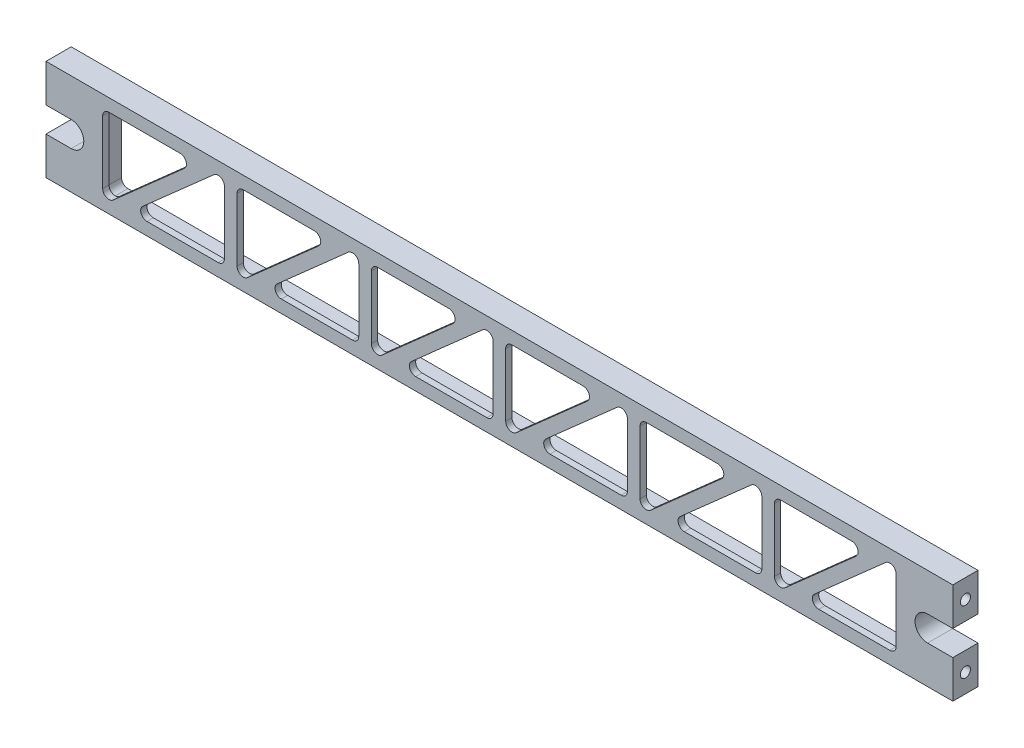
SolidWorks part; units mm, degrees
material "6061 Alloy"
ref_plane "Front Plane" through (0, 0, 0) normal (0, 0, 1) x (1, 0, 0)
ref_plane "Top Plane" through (0, 0, 0) normal (0, 1, 0) x (1, 0, 0)
ref_plane "Right Plane" through (0, 0, 0) normal (1, 0, 0) x (0, 0, -1)
sketch "Sketch1" plane through (0, 0, 0) normal (1, 0, 0) x (0, 0, -1)
  line L1 (0, 0) -> (12.7, 0)
  line L2 (0, 0) -> (0, 50.8)
  line L3 (0, 50.8) -> (12.7, 50.8)
  line L4 (12.7, 0) -> (12.7, 50.8)
  dimension "D1" = 12.7
  dimension "D2" = 50.8
extrude "Boss-Extrude1" add sketch "Sketch1" along normal mid plane 457.2
hole_wizard "1/4-20 Tapped Hole1" positions "3DSketch1" profile "Sketch2" tap size "1/4-20" standard "ANSI Inch"
sketch3d "3DSketch1"
  line L2 (228.6, 9.525, -6.35) -> (228.6, 41.275, -6.35) construction
  line L4 (228.6, 41.275, -6.35) -> (228.6, 50.8, -6.35) construction
  line L5 (228.6, 50.8, -12.7) -> (228.6, 50.8, 0) construction
  line L8 (228.6, 9.525, -6.35) -> (228.6, 0, -6.35) construction
  line L9 (228.6, 0, 0) -> (228.6, 0, -12.7) construction
  point P0 (228.6, 41.275, -6.35)
  point P2 (228.6, 9.525, -6.35)
  point P4 (-228.6, 9.525, -6.35)
  point P6 (-228.6, 41.275, -6.35)
  dimension "D1" = 31.75
sketch "Sketch2" plane through (228.6, 41.275, -6.35) normal (0, 1, 0) x (0, 0, -1)
  line L0 (0, 0) -> (0, 20.5838)
  line L1 (0, 20.5838) -> (2.5527, 19.05)
  line L2 (2.5527, 19.05) -> (2.5527, 0)
  line L5 (2.5527, 0) -> (0, 0)
  line L10 (0, 20.5838) -> (-2.5527, 19.05) construction
  line L11 (0, -6.35) -> (0, 107.95) construction
  dimension "Tap Drill Dia." = 5.1054
  dimension "Tap Drill Depth" = 19.05
  dimension "Drill Angle" = 118
sketch "Sketch4" plane through (0, 0, -12.7) normal (0, 0, -1) x (-1, 0, 0)
  line L0 (0, 0) -> (0, 3.175) construction
  line L1 (200.025, 47.625) -> (-200.025, 47.625)
  line L2 (203.2, 44.45) -> (203.2, 6.35)
  line L3 (200.025, 3.175) -> (-200.025, 3.175)
  line L4 (-203.2, 44.45) -> (-203.2, 6.35)
  line L5 (-228.6, 0) -> (228.6, 0) construction
  line L6 (0, 47.625) -> (0, 50.8) construction
  line L7 (-228.6, 50.8) -> (228.6, 50.8) construction
  line L8 (228.6, 25.4) -> (203.2, 25.4) construction
  line L9 (228.6, 0) -> (228.6, 50.8) construction
  line L10 (-228.6, 25.4) -> (-203.2, 25.4) construction
  line L11 (-228.6, 0) -> (-228.6, 50.8) construction
  arc A0 (-200.025, 3.175) -> (-203.2, 6.35) centre (-200.025, 6.35) cw
  arc A1 (-200.025, 47.625) -> (-203.2, 44.45) centre (-200.025, 44.45) ccw
  arc A2 (203.2, 6.35) -> (200.025, 3.175) centre (200.025, 6.35) cw
  arc A3 (200.025, 47.625) -> (203.2, 44.45) centre (200.025, 44.45) cw
  dimension "D1" = 3.175
  dimension "D2" = 3.175
  dimension "D3" = 25.4
extrude "Cut-Extrude1" cut sketch "Sketch4" against normal blind 9.525
sketch "Sketch5" plane through (0, 0, -3.175) normal (0, 0, -1) x (-1, 0, 0)
  line L0 (-200.025, 41.275) -> (-200.025, 9.525)
  line L1 (-196.85, 6.35) -> (-160.9784, 6.35)
  line L2 (-158.8741, 11.9025) -> (-194.7457, 43.6525)
  line L3 (-179.7926, 38.8975) -> (-143.921, 7.1475)
  line L4 (-138.6417, 9.525) -> (-138.6417, 41.275)
  line L5 (-141.8167, 44.45) -> (-177.6882, 44.45)
  line L6 (-132.2917, 41.275) -> (-132.2917, 9.525)
  line L7 (-159.7525, 44.45) -> (-159.7525, 47.625) construction
  line L8 (200.025, 47.625) -> (-200.025, 47.625) construction
  line L9 (-129.1167, 6.35) -> (-93.2451, 6.35)
  line L10 (-178.9142, 6.35) -> (-178.9142, 3.175) construction
  line L11 (-200.025, 3.175) -> (200.025, 3.175) construction
  line L12 (-91.1408, 11.9025) -> (-127.0123, 43.6525)
  line L13 (-200.025, 25.4) -> (-203.2, 25.4) construction
  line L14 (-203.2, 44.45) -> (-203.2, 6.35) construction
  line L15 (-176.8099, 27.7775) -> (-172.6013, 32.5325) construction
  line L16 (-112.0592, 38.8975) -> (-76.1877, 7.1475)
  line L17 (-70.9083, 9.525) -> (-70.9083, 41.275)
  line L18 (-74.0833, 44.45) -> (-109.9549, 44.45)
  line L19 (-109.0766, 27.7775) -> (-104.8679, 32.5325) construction
  line L20 (-64.5583, 41.275) -> (-64.5583, 9.525)
  line L21 (-61.3833, 6.35) -> (-25.5118, 6.35)
  line L22 (-23.4074, 11.9025) -> (-59.279, 43.6525)
  line L23 (-44.3259, 38.8975) -> (-8.4543, 7.1475)
  line L24 (-3.175, 9.525) -> (-3.175, 41.275)
  line L25 (-6.35, 44.45) -> (-42.2216, 44.45)
  line L26 (-41.3432, 27.7775) -> (-37.1346, 32.5325) construction
  line L27 (3.175, 41.275) -> (3.175, 9.525)
  line L28 (6.35, 6.35) -> (42.2216, 6.35)
  line L29 (44.3259, 11.9025) -> (8.4543, 43.6525)
  line L30 (23.4074, 38.8975) -> (59.279, 7.1475)
  line L31 (64.5583, 9.525) -> (64.5583, 41.275)
  line L32 (61.3833, 44.45) -> (25.5118, 44.45)
  line L33 (26.3901, 27.7775) -> (30.5987, 32.5325) construction
  line L34 (70.9083, 41.275) -> (70.9083, 9.525)
  line L35 (74.0833, 6.35) -> (109.9549, 6.35)
  line L36 (112.0592, 11.9025) -> (76.1877, 43.6525)
  line L37 (91.1408, 38.8975) -> (127.0123, 7.1475)
  line L38 (132.2917, 9.525) -> (132.2917, 41.275)
  line L39 (129.1167, 44.45) -> (93.2451, 44.45)
  line L40 (94.1234, 27.7775) -> (98.3321, 32.5325) construction
  line L41 (138.6417, 41.275) -> (138.6417, 9.525)
  line L42 (141.8167, 6.35) -> (177.6882, 6.35)
  line L43 (179.7926, 11.9025) -> (143.921, 43.6525)
  line L44 (158.8741, 38.8975) -> (194.7457, 7.1475)
  line L45 (200.025, 9.525) -> (200.025, 41.275)
  line L46 (196.85, 44.45) -> (160.9784, 44.45)
  line L47 (161.8568, 27.7775) -> (166.0654, 32.5325) construction
  line L48 (-138.6417, 25.4) -> (-132.2917, 25.4) construction
  line L49 (200.025, 25.4) -> (203.2, 25.4) construction
  line L50 (203.2, 6.35) -> (203.2, 44.45) construction
  arc A0 (-179.7926, 38.8975) -> (-177.6882, 44.45) centre (-177.6882, 41.275) cw
  arc A1 (-138.6417, 41.275) -> (-141.8167, 44.45) centre (-141.8167, 41.275) ccw
  arc A2 (-143.921, 7.1475) -> (-138.6417, 9.525) centre (-141.8167, 9.525) ccw
  arc A3 (-160.9784, 6.35) -> (-158.8741, 11.9025) centre (-160.9784, 9.525) ccw
  arc A4 (-200.025, 9.525) -> (-196.85, 6.35) centre (-196.85, 9.525) ccw
  arc A5 (-200.025, 41.275) -> (-194.7457, 43.6525) centre (-196.85, 41.275) cw
  arc A6 (-112.0592, 38.8975) -> (-109.9549, 44.45) centre (-109.9549, 41.275) cw
  arc A7 (-70.9083, 41.275) -> (-74.0833, 44.45) centre (-74.0833, 41.275) ccw
  arc A8 (-76.1877, 7.1475) -> (-70.9083, 9.525) centre (-74.0833, 9.525) ccw
  arc A9 (-93.2451, 6.35) -> (-91.1408, 11.9025) centre (-93.2451, 9.525) ccw
  arc A10 (-132.2917, 9.525) -> (-129.1167, 6.35) centre (-129.1167, 9.525) ccw
  arc A11 (-132.2917, 41.275) -> (-127.0123, 43.6525) centre (-129.1167, 41.275) cw
  arc A12 (-44.3259, 38.8975) -> (-42.2216, 44.45) centre (-42.2216, 41.275) cw
  arc A13 (-3.175, 41.275) -> (-6.35, 44.45) centre (-6.35, 41.275) ccw
  arc A14 (-8.4543, 7.1475) -> (-3.175, 9.525) centre (-6.35, 9.525) ccw
  arc A15 (-25.5118, 6.35) -> (-23.4074, 11.9025) centre (-25.5118, 9.525) ccw
  arc A16 (-64.5583, 9.525) -> (-61.3833, 6.35) centre (-61.3833, 9.525) ccw
  arc A17 (-64.5583, 41.275) -> (-59.279, 43.6525) centre (-61.3833, 41.275) cw
  arc A18 (23.4074, 38.8975) -> (25.5118, 44.45) centre (25.5118, 41.275) cw
  arc A19 (64.5583, 41.275) -> (61.3833, 44.45) centre (61.3833, 41.275) ccw
  arc A20 (59.279, 7.1475) -> (64.5583, 9.525) centre (61.3833, 9.525) ccw
  arc A21 (42.2216, 6.35) -> (44.3259, 11.9025) centre (42.2216, 9.525) ccw
  arc A22 (3.175, 9.525) -> (6.35, 6.35) centre (6.35, 9.525) ccw
  arc A23 (3.175, 41.275) -> (8.4543, 43.6525) centre (6.35, 41.275) cw
  arc A24 (91.1408, 38.8975) -> (93.2451, 44.45) centre (93.2451, 41.275) cw
  arc A25 (132.2917, 41.275) -> (129.1167, 44.45) centre (129.1167, 41.275) ccw
  arc A26 (127.0123, 7.1475) -> (132.2917, 9.525) centre (129.1167, 9.525) ccw
  arc A27 (109.9549, 6.35) -> (112.0592, 11.9025) centre (109.9549, 9.525) ccw
  arc A28 (70.9083, 9.525) -> (74.0833, 6.35) centre (74.0833, 9.525) ccw
  arc A29 (70.9083, 41.275) -> (76.1877, 43.6525) centre (74.0833, 41.275) cw
  arc A30 (158.8741, 38.8975) -> (160.9784, 44.45) centre (160.9784, 41.275) cw
  arc A31 (200.025, 41.275) -> (196.85, 44.45) centre (196.85, 41.275) ccw
  arc A32 (194.7457, 7.1475) -> (200.025, 9.525) centre (196.85, 9.525) ccw
  arc A33 (177.6882, 6.35) -> (179.7926, 11.9025) centre (177.6882, 9.525) ccw
  arc A34 (138.6417, 9.525) -> (141.8167, 6.35) centre (141.8167, 9.525) ccw
  arc A35 (138.6417, 41.275) -> (143.921, 43.6525) centre (141.8167, 41.275) cw
  dimension "D1" = 3.175
  dimension "D2" = 3.175
  dimension "D4" = 6
  dimension "D3" = 6.35
extrude "Cut-Extrude2" cut sketch "Sketch5" against normal through all
sketch "Sketch6" plane through (0, 0, 0) normal (0, 0, 1) x (1, 0, 0)
  line L0 (0, 0) -> (0, 50.8) construction
  line L1 (228.6, 50.8) -> (-228.6, 50.8) construction
  line L2 (-215.9, 31.75) -> (-228.6, 31.75)
  line L3 (-228.6, 50.8) -> (-228.6, 0) construction
  line L4 (-228.6, 31.75) -> (-228.6, 19.05)
  line L5 (-228.6, 19.05) -> (-215.9, 19.05)
  line L6 (228.6, 19.05) -> (215.9, 19.05)
  line L7 (-203.2, 6.35) -> (-203.2, 44.45) construction
  line L8 (228.6, 31.75) -> (228.6, 19.05)
  line L9 (215.9, 31.75) -> (228.6, 31.75)
  arc A0 (-215.9, 19.05) -> (-215.9, 31.75) centre (-215.9, 25.4) ccw
  arc A1 (215.9, 19.05) -> (215.9, 31.75) centre (215.9, 25.4) cw
  point P8 (-228.6, 25.4)
  point P18 (228.6, 25.4)
  point P19 (-209.55, 25.4)
  dimension "D1" = 12.7
  dimension "D2" = 6.35
extrude "Cut-Extrude3" cut sketch "Sketch6" against normal through all
